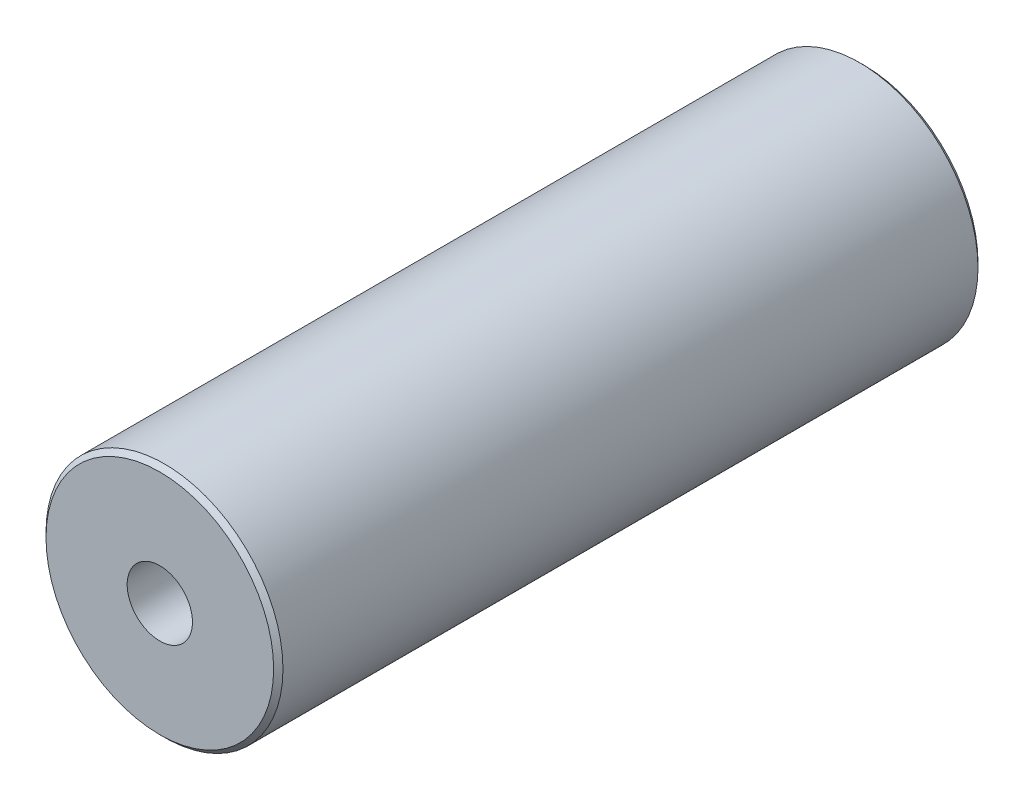
SolidWorks part; units mm, degrees
material "AISI 304 Stainless Steel"
ref_plane "Front Plane" through (0, 0, 0) normal (0, 0, 1) x (1, 0, 0)
ref_plane "Top Plane" through (0, 0, 0) normal (0, 1, 0) x (1, 0, 0)
ref_plane "Right Plane" through (0, 0, 0) normal (1, 0, 0) x (0, 0, -1)
ref_axis "Axis1" through (0, 0, -88.99) along (0, 0, 1)
ref_axis "Axis2" through (0, -55, 0) along (0, 1, 0)
ref_axis "Axis3" through (-88.99, 0, 0) along (1, 0, 0)
sketch "Sketch1" plane through (0, 0, 0) normal (0, 0, 1) x (1, 0, 0)
  circle A0 centre (0, 0) radius 12.7
  dimension "D1" = 25.4
extrude "Boss-Extrude1" add sketch "Sketch1" along normal mid plane 75.5
hole_wizard "M8x1.0 Tapped Hole1" positions "Sketch3" profile "Sketch2" tap size "M8x1.0" standard "ANSI Metric"
sketch "Sketch3" plane through (0, 0, 37.75) normal (0, 0, 1) x (1, 0, 0)
  point P0 (0, 0)
sketch "Sketch2" plane through (0, 0, 37.75) normal (1, 0, 0) x (0, -1, 0)
  line L0 (0, 0) -> (0, 14.103)
  line L1 (0, 14.103) -> (3.5, 12)
  line L2 (3.5, 12) -> (3.5, 0)
  line L5 (3.5, 0) -> (0, 0)
  line L10 (0, 14.103) -> (-3.5, 12) construction
  line L11 (0, -6.35) -> (0, 107.95) construction
  dimension "Tap Drill Dia." = 7
  dimension "Tap Drill Depth" = 12
  dimension "Drill Angle" = 118
cosmetic thread "Hole Thread1" parameters "D1"=10, "D2"=8
mirror "Mirror1" about plane through (0, 0, 0) normal (0, 0, 1) of "M8x1.0 Tapped Hole1"
chamfer "Chamfer1" distance 0.5 angle 45 2 edges at (12.7, 0, -37.75) (12.7, 0, 37.75)
